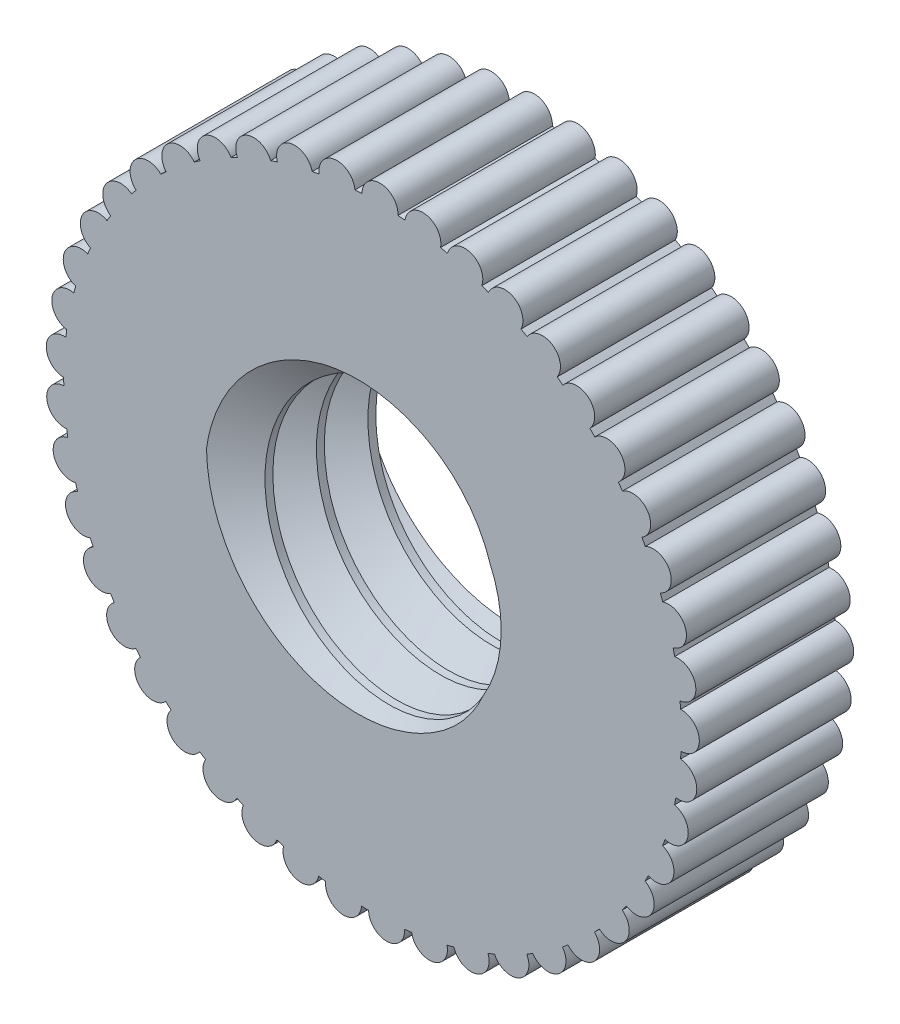
SolidWorks part; units mm, degrees
ref_plane "Front" through (0, 0, 0) normal (0, 0, 1) x (1, 0, 0)
ref_plane "Top" through (0, 0, 0) normal (0, 1, 0) x (1, 0, 0)
ref_plane "Right" through (0, 0, 0) normal (1, 0, 0) x (0, 0, -1)
sketch "Sketch1" plane through (0, 0, 0) normal (0, 0, 1) x (1, 0, 0)
  circle A0 centre (0, 0) radius 1.25
  circle A1 centre (0, 0) radius 3
  dimension "D1" = 2.5
  dimension "D2" = 6
extrude "Boss-Extrude1" add sketch "Sketch1" along normal blind 1.5
sketch "Sketch2" plane through (0, 0, 1.5) normal (0, 0, 1) x (1, 0, 0)
  circle A0 centre (0, 0) radius 1.25 construction
  circle A1 centre (0, 0) radius 1.25
curve "Helix/Spiral1" pitch 0.5 height 2 radius 1.25 centre (0, 0, 1.5) axis (0, 0, -1) start towards (-1, 0, 0)
ref_plane "Plane1" through (-1.25, 0, 1.5) normal (0, 0.998, -0.0635) x (1, 0, 0)
sketch "Sketch3" plane through (-1.25, 0, 1.5) normal (0, 0.998, -0.0635) x (1, 0, 0)
  line L1 (-0.3661, -0.0045) -> (0.0496, -0.2445)
  line L2 (0.0496, -0.2445) -> (0.0496, 0.2355)
  line L3 (0.0496, 0.2355) -> (-0.3661, -0.0045)
  circle A0 centre (-0.0889, -0.0045) radius 0.1386 construction
  point P1 (-0.084, -0.0043)
  point P6 (-0.0889, -0.0045)
  dimension "D1" = 0.48
sweep "Cut-Sweep1" cut profiles "Sketch3" path "Helix/Spiral1" align with end faces yes
sketch "Sketch4" plane through (0, 0, 1.5) normal (0, 0, 1) x (1, 0, 0)
  circle A0 centre (-2.9903, -0.2414) radius 0.175
  circle A1 centre (0, 0) radius 3 construction
  circle A2 centre (-2.9948, 0.1772) radius 0.175
  circle A3 centre (-2.941, 0.5922) radius 0.175
  circle A4 centre (-2.8299, 0.9958) radius 0.175
  circle A5 centre (-2.6638, 1.3799) radius 0.175
  circle A6 centre (-2.4458, 1.7372) radius 0.175
  circle A7 centre (-2.1803, 2.0607) radius 0.175
  circle A8 centre (-1.8722, 2.3441) radius 0.175
  circle A9 centre (-1.5278, 2.5818) radius 0.175
  circle A10 centre (-1.1536, 2.7693) radius 0.175
  circle A11 centre (-0.7569, 2.9029) radius 0.175
  circle A12 centre (-0.3456, 2.98) radius 0.175
  circle A13 centre (0.0725, 2.9991) radius 0.175
  circle A14 centre (0.4892, 2.9598) radius 0.175
  circle A15 centre (0.8964, 2.8629) radius 0.175
  circle A16 centre (1.2861, 2.7103) radius 0.175
  circle A17 centre (1.6508, 2.505) radius 0.175
  circle A18 centre (1.9834, 2.2508) radius 0.175
  circle A19 centre (2.2773, 1.9529) radius 0.175
  circle A20 centre (2.5269, 1.617) radius 0.175
  circle A21 centre (2.7274, 1.2495) radius 0.175
  circle A22 centre (2.8747, 0.8578) radius 0.175
  circle A23 centre (2.9662, 0.4494) radius 0.175
  circle A24 centre (2.9998, 0.0322) radius 0.175
  circle A25 centre (2.9751, -0.3856) radius 0.175
  circle A26 centre (2.8925, -0.7959) radius 0.175
  circle A27 centre (2.7536, -1.1907) radius 0.175
  circle A28 centre (2.5611, -1.5624) radius 0.175
  circle A29 centre (2.3187, -1.9036) radius 0.175
  circle A30 centre (2.0312, -2.2078) radius 0.175
  circle A31 centre (1.7042, -2.469) radius 0.175
  circle A32 centre (1.344, -2.6821) radius 0.175
  circle A33 centre (0.9576, -2.8431) radius 0.175
  circle A34 centre (0.5526, -2.9487) radius 0.175
  circle A35 centre (0.1369, -2.9969) radius 0.175
  circle A36 centre (-0.2816, -2.9868) radius 0.175
  circle A37 centre (-0.6945, -2.9185) radius 0.175
  circle A38 centre (-1.0939, -2.7934) radius 0.175
  circle A39 centre (-1.472, -2.614) radius 0.175
  circle A40 centre (-1.8215, -2.3837) radius 0.175
  circle A41 centre (-2.1355, -2.107) radius 0.175
  circle A42 centre (-2.408, -1.7893) radius 0.175
  circle A43 centre (-2.6336, -1.4367) radius 0.175
  circle A44 centre (-2.8079, -1.0562) radius 0.175
  circle A45 centre (-2.9276, -0.6552) radius 0.175
  point P94 (0, 0)
  dimension "D1" = 0.35
  dimension "D2" = 45
extrude "Boss-Extrude2" add sketch "Sketch4" against normal up to surface (1.5 mm away) up to face at (3, 0, 0)
